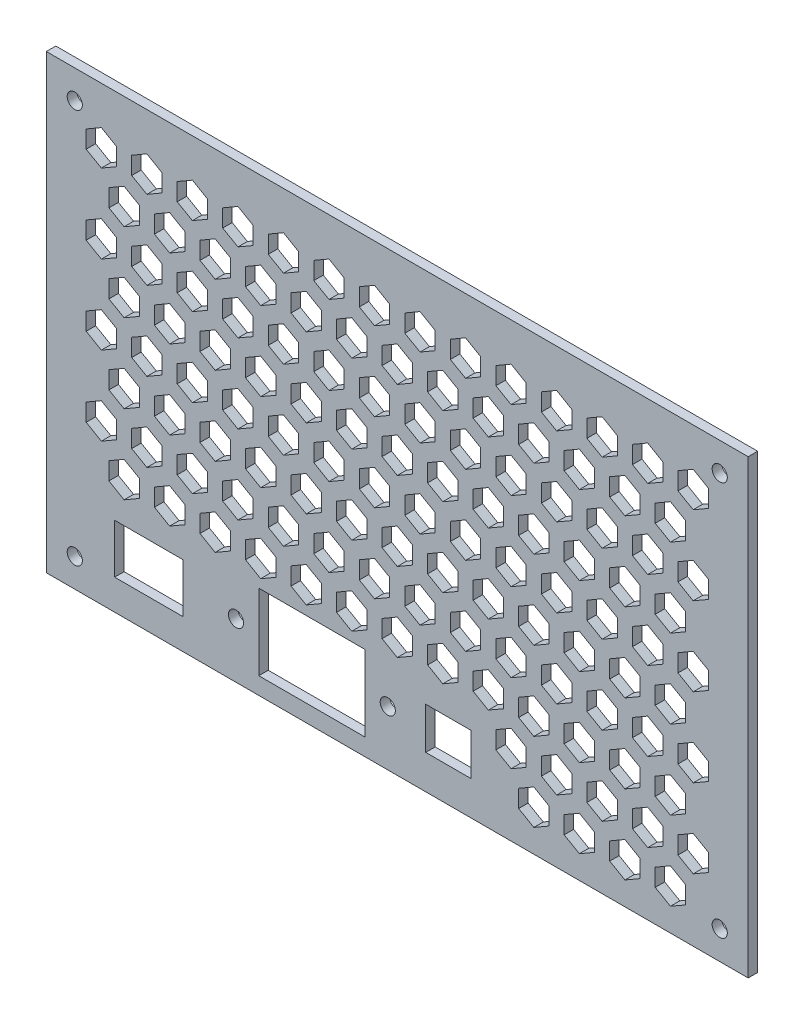
SolidWorks part; units mm, degrees
ref_plane "Front Plane" through (0, 0, 0) normal (0, 0, 1) x (1, 0, 0)
ref_plane "Top Plane" through (0, 0, 0) normal (0, 1, 0) x (1, 0, 0)
ref_plane "Right Plane" through (0, 0, 0) normal (1, 0, 0) x (0, 0, -1)
sketch "Sketch1" plane through (0, 0, 0) normal (0, 0, 1) x (1, 0, 0)
  line L1 (-92.5, -57.5) -> (92.5, -57.5)
  line L2 (-92.5, -57.5) -> (-92.5, 57.5)
  line L3 (-92.5, 57.5) -> (92.5, 57.5)
  line L4 (92.5, -57.5) -> (92.5, 57.5)
  line L5 (-92.5, -57.5) -> (92.5, 57.5) construction
  line L6 (-92.5, 57.5) -> (92.5, -57.5) construction
  point P0 (0, 0)
  dimension "D1" = 185
  dimension "D2" = 115
extrude "Boss-Extrude1" add sketch "Sketch1" along normal blind 2.5
sketch "Sketch2" plane through (0, 0, 0) normal (0, 0, -1) x (-1, 0, 0)
  line L0 (92.5, 57.5) -> (92.5, -57.5) construction
  line L1 (74.5, -36.5) -> (56.5, -36.5)
  line L2 (74.5, -36.5) -> (74.5, -49.5)
  line L3 (74.5, -49.5) -> (56.5, -49.5)
  line L4 (56.5, -36.5) -> (56.5, -49.5)
  line L5 (74.5, -36.5) -> (56.5, -49.5) construction
  line L6 (74.5, -49.5) -> (56.5, -36.5) construction
  line L8 (92.5, -57.5) -> (-92.5, -57.5) construction
  line L9 (36.5, -33) -> (8.5, -33)
  line L10 (36.5, -33) -> (36.5, -53)
  line L11 (36.5, -53) -> (8.5, -53)
  line L12 (8.5, -33) -> (8.5, -53)
  line L13 (36.5, -33) -> (8.5, -53) construction
  line L14 (36.5, -53) -> (8.5, -33) construction
  circle A0 centre (42.5, -43) radius 2
  circle A1 centre (2.5, -43) radius 2
  point P0 (65.5, -43)
  point P9 (22.5, -43)
  dimension "D7" = 4
  dimension "D8" = 4
  dimension "D9" = 20
  dimension "D10" = 20
  dimension "D1" = 18
  dimension "D2" = 13
  dimension "D3" = 18
  dimension "D4" = 8
  dimension "D5" = 28
  dimension "D6" = 20
  dimension "D11" = 70
extrude "Cut-Extrude1" cut sketch "Sketch2" against normal blind 10
sketch "Sketch4" plane through (0, 0, 0) normal (0, 0, -1) x (-1, 0, 0)
  text T0 "BACK" font "Century Gothic" height in points 72
extrude "Cut-Extrude2" [suppressed] cut sketch "Sketch4" against normal blind 1
sketch "Sketch5" plane through (0, 0, 0) normal (0, 0, -1) x (-1, 0, 0)
  line L24 (-72, 40.9827) -> (-76, 38.6733)
  line L25 (-78, 51.375) -> (-82, 49.0656)
  line L26 (-82, 49.0656) -> (-82, 44.4468)
  line L27 (-82, 44.4468) -> (-78, 42.1374)
  line L28 (-78, 42.1374) -> (-74, 44.4468)
  line L29 (-74, 44.4468) -> (-74, 49.0656)
  line L30 (-74, 49.0656) -> (-78, 51.375)
  line L31 (-76, 38.6733) -> (-76, 34.0545)
  line L32 (-76, 34.0545) -> (-72, 31.7451)
  line L33 (-72, 31.7451) -> (-68, 34.0545)
  line L34 (-68, 34.0545) -> (-68, 38.6733)
  line L35 (-68, 38.6733) -> (-72, 40.9827)
  line L36 (-60, 40.9827) -> (-64, 38.6733)
  line L37 (-66, 51.375) -> (-70, 49.0656)
  line L38 (-70, 49.0656) -> (-70, 44.4468)
  line L39 (-70, 44.4468) -> (-66, 42.1374)
  line L40 (-66, 42.1374) -> (-62, 44.4468)
  line L41 (-62, 44.4468) -> (-62, 49.0656)
  line L42 (-62, 49.0656) -> (-66, 51.375)
  line L43 (-64, 38.6733) -> (-64, 34.0545)
  line L44 (-64, 34.0545) -> (-60, 31.7451)
  line L45 (-60, 31.7451) -> (-56, 34.0545)
  line L46 (-56, 34.0545) -> (-56, 38.6733)
  line L47 (-56, 38.6733) -> (-60, 40.9827)
  line L48 (-48, 40.9827) -> (-52, 38.6733)
  line L49 (-54, 51.375) -> (-58, 49.0656)
  line L50 (-58, 49.0656) -> (-58, 44.4468)
  line L51 (-58, 44.4468) -> (-54, 42.1374)
  line L52 (-54, 42.1374) -> (-50, 44.4468)
  line L53 (-50, 44.4468) -> (-50, 49.0656)
  line L54 (-50, 49.0656) -> (-54, 51.375)
  line L55 (-52, 38.6733) -> (-52, 34.0545)
  line L56 (-52, 34.0545) -> (-48, 31.7451)
  line L57 (-48, 31.7451) -> (-44, 34.0545)
  line L58 (-44, 34.0545) -> (-44, 38.6733)
  line L59 (-44, 38.6733) -> (-48, 40.9827)
  line L60 (-36, 40.9827) -> (-40, 38.6733)
  line L61 (-42, 51.375) -> (-46, 49.0656)
  line L62 (-46, 49.0656) -> (-46, 44.4468)
  line L63 (-46, 44.4468) -> (-42, 42.1374)
  line L64 (-42, 42.1374) -> (-38, 44.4468)
  line L65 (-38, 44.4468) -> (-38, 49.0656)
  line L66 (-38, 49.0656) -> (-42, 51.375)
  line L67 (-40, 38.6733) -> (-40, 34.0545)
  line L68 (-40, 34.0545) -> (-36, 31.7451)
  line L69 (-36, 31.7451) -> (-32, 34.0545)
  line L70 (-32, 34.0545) -> (-32, 38.6733)
  line L71 (-32, 38.6733) -> (-36, 40.9827)
  line L72 (-24, 40.9827) -> (-28, 38.6733)
  line L73 (-30, 51.375) -> (-34, 49.0656)
  line L74 (-34, 49.0656) -> (-34, 44.4468)
  line L75 (-34, 44.4468) -> (-30, 42.1374)
  line L76 (-30, 42.1374) -> (-26, 44.4468)
  line L77 (-26, 44.4468) -> (-26, 49.0656)
  line L78 (-26, 49.0656) -> (-30, 51.375)
  line L79 (-28, 38.6733) -> (-28, 34.0545)
  line L80 (-28, 34.0545) -> (-24, 31.7451)
  line L81 (-24, 31.7451) -> (-20, 34.0545)
  line L82 (-20, 34.0545) -> (-20, 38.6733)
  line L83 (-20, 38.6733) -> (-24, 40.9827)
  line L84 (-12, 40.9827) -> (-16, 38.6733)
  line L85 (-18, 51.375) -> (-22, 49.0656)
  line L86 (-22, 49.0656) -> (-22, 44.4468)
  line L87 (-22, 44.4468) -> (-18, 42.1374)
  line L88 (-18, 42.1374) -> (-14, 44.4468)
  line L89 (-14, 44.4468) -> (-14, 49.0656)
  line L90 (-14, 49.0656) -> (-18, 51.375)
  line L91 (-16, 38.6733) -> (-16, 34.0545)
  line L92 (-16, 34.0545) -> (-12, 31.7451)
  line L93 (-12, 31.7451) -> (-8, 34.0545)
  line L94 (-8, 34.0545) -> (-8, 38.6733)
  line L95 (-8, 38.6733) -> (-12, 40.9827)
  line L96 (0, 40.9827) -> (-4, 38.6733)
  line L97 (-6, 51.375) -> (-10, 49.0656)
  line L98 (-10, 49.0656) -> (-10, 44.4468)
  line L99 (-10, 44.4468) -> (-6, 42.1374)
  line L100 (-6, 42.1374) -> (-2, 44.4468)
  line L101 (-2, 44.4468) -> (-2, 49.0656)
  line L102 (-2, 49.0656) -> (-6, 51.375)
  line L103 (-4, 38.6733) -> (-4, 34.0545)
  line L104 (-4, 34.0545) -> (0, 31.7451)
  line L105 (0, 31.7451) -> (4, 34.0545)
  line L106 (4, 34.0545) -> (4, 38.6733)
  line L107 (4, 38.6733) -> (0, 40.9827)
  line L108 (12, 40.9827) -> (8, 38.6733)
  line L109 (6, 51.375) -> (2, 49.0656)
  line L110 (2, 49.0656) -> (2, 44.4468)
  line L111 (2, 44.4468) -> (6, 42.1374)
  line L112 (6, 42.1374) -> (10, 44.4468)
  line L113 (10, 44.4468) -> (10, 49.0656)
  line L114 (10, 49.0656) -> (6, 51.375)
  line L115 (8, 38.6733) -> (8, 34.0545)
  line L116 (8, 34.0545) -> (12, 31.7451)
  line L117 (12, 31.7451) -> (16, 34.0545)
  line L118 (16, 34.0545) -> (16, 38.6733)
  line L119 (16, 38.6733) -> (12, 40.9827)
  line L120 (24, 40.9827) -> (20, 38.6733)
  line L121 (18, 51.375) -> (14, 49.0656)
  line L122 (14, 49.0656) -> (14, 44.4468)
  line L123 (14, 44.4468) -> (18, 42.1374)
  line L124 (18, 42.1374) -> (22, 44.4468)
  line L125 (22, 44.4468) -> (22, 49.0656)
  line L126 (22, 49.0656) -> (18, 51.375)
  line L127 (20, 38.6733) -> (20, 34.0545)
  line L128 (20, 34.0545) -> (24, 31.7451)
  line L129 (24, 31.7451) -> (28, 34.0545)
  line L130 (28, 34.0545) -> (28, 38.6733)
  line L131 (28, 38.6733) -> (24, 40.9827)
  line L132 (36, 40.9827) -> (32, 38.6733)
  line L133 (30, 51.375) -> (26, 49.0656)
  line L134 (26, 49.0656) -> (26, 44.4468)
  line L135 (26, 44.4468) -> (30, 42.1374)
  line L136 (30, 42.1374) -> (34, 44.4468)
  line L137 (34, 44.4468) -> (34, 49.0656)
  line L138 (34, 49.0656) -> (30, 51.375)
  line L139 (32, 38.6733) -> (32, 34.0545)
  line L140 (32, 34.0545) -> (36, 31.7451)
  line L141 (36, 31.7451) -> (40, 34.0545)
  line L142 (40, 34.0545) -> (40, 38.6733)
  line L143 (40, 38.6733) -> (36, 40.9827)
  line L144 (48, 40.9827) -> (44, 38.6733)
  line L145 (42, 51.375) -> (38, 49.0656)
  line L146 (38, 49.0656) -> (38, 44.4468)
  line L147 (38, 44.4468) -> (42, 42.1374)
  line L148 (42, 42.1374) -> (46, 44.4468)
  line L149 (46, 44.4468) -> (46, 49.0656)
  line L150 (46, 49.0656) -> (42, 51.375)
  line L151 (44, 38.6733) -> (44, 34.0545)
  line L152 (44, 34.0545) -> (48, 31.7451)
  line L153 (48, 31.7451) -> (52, 34.0545)
  line L154 (52, 34.0545) -> (52, 38.6733)
  line L155 (52, 38.6733) -> (48, 40.9827)
  line L156 (60, 40.9827) -> (56, 38.6733)
  line L157 (54, 51.375) -> (50, 49.0656)
  line L158 (50, 49.0656) -> (50, 44.4468)
  line L159 (50, 44.4468) -> (54, 42.1374)
  line L160 (54, 42.1374) -> (58, 44.4468)
  line L161 (58, 44.4468) -> (58, 49.0656)
  line L162 (58, 49.0656) -> (54, 51.375)
  line L163 (56, 38.6733) -> (56, 34.0545)
  line L164 (56, 34.0545) -> (60, 31.7451)
  line L165 (60, 31.7451) -> (64, 34.0545)
  line L166 (64, 34.0545) -> (64, 38.6733)
  line L167 (64, 38.6733) -> (60, 40.9827)
  line L168 (72, 40.9827) -> (68, 38.6733)
  line L169 (66, 51.375) -> (62, 49.0656)
  line L170 (62, 49.0656) -> (62, 44.4468)
  line L171 (62, 44.4468) -> (66, 42.1374)
  line L172 (66, 42.1374) -> (70, 44.4468)
  line L173 (70, 44.4468) -> (70, 49.0656)
  line L174 (70, 49.0656) -> (66, 51.375)
  line L175 (68, 38.6733) -> (68, 34.0545)
  line L176 (68, 34.0545) -> (72, 31.7451)
  line L177 (72, 31.7451) -> (76, 34.0545)
  line L178 (76, 34.0545) -> (76, 38.6733)
  line L179 (76, 38.6733) -> (72, 40.9827)
  line L180 (-60, 20.2027) -> (-64, 17.8933)
  line L181 (-66, 30.595) -> (-70, 28.2856)
  line L182 (-70, 28.2856) -> (-70, 23.6668)
  line L183 (-70, 23.6668) -> (-66, 21.3574)
  line L184 (-66, 21.3574) -> (-62, 23.6668)
  line L185 (-62, 23.6668) -> (-62, 28.2856)
  line L186 (-62, 28.2856) -> (-66, 30.595)
  line L187 (-64, 17.8933) -> (-64, 13.2745)
  line L188 (-64, 13.2745) -> (-60, 10.9651)
  line L189 (-60, 10.9651) -> (-56, 13.2745)
  line L190 (-56, 13.2745) -> (-56, 17.8933)
  line L191 (-56, 17.8933) -> (-60, 20.2027)
  line L192 (-48, 20.2027) -> (-52, 17.8933)
  line L193 (-54, 30.595) -> (-58, 28.2856)
  line L194 (-58, 28.2856) -> (-58, 23.6668)
  line L195 (-58, 23.6668) -> (-54, 21.3574)
  line L196 (-54, 21.3574) -> (-50, 23.6668)
  line L197 (-50, 23.6668) -> (-50, 28.2856)
  line L198 (-50, 28.2856) -> (-54, 30.595)
  line L199 (-52, 17.8933) -> (-52, 13.2745)
  line L200 (-52, 13.2745) -> (-48, 10.9651)
  line L201 (-48, 10.9651) -> (-44, 13.2745)
  line L202 (-44, 13.2745) -> (-44, 17.8933)
  line L203 (-44, 17.8933) -> (-48, 20.2027)
  line L204 (-36, 20.2027) -> (-40, 17.8933)
  line L205 (-42, 30.595) -> (-46, 28.2856)
  line L206 (-46, 28.2856) -> (-46, 23.6668)
  line L207 (-46, 23.6668) -> (-42, 21.3574)
  line L208 (-42, 21.3574) -> (-38, 23.6668)
  line L209 (-38, 23.6668) -> (-38, 28.2856)
  line L210 (-38, 28.2856) -> (-42, 30.595)
  line L211 (-40, 17.8933) -> (-40, 13.2745)
  line L212 (-40, 13.2745) -> (-36, 10.9651)
  line L213 (-36, 10.9651) -> (-32, 13.2745)
  line L214 (-32, 13.2745) -> (-32, 17.8933)
  line L215 (-32, 17.8933) -> (-36, 20.2027)
  line L216 (-24, 20.2027) -> (-28, 17.8933)
  line L217 (-30, 30.595) -> (-34, 28.2856)
  line L218 (-34, 28.2856) -> (-34, 23.6668)
  line L219 (-34, 23.6668) -> (-30, 21.3574)
  line L220 (-30, 21.3574) -> (-26, 23.6668)
  line L221 (-26, 23.6668) -> (-26, 28.2856)
  line L222 (-26, 28.2856) -> (-30, 30.595)
  line L223 (-28, 17.8933) -> (-28, 13.2745)
  line L224 (-28, 13.2745) -> (-24, 10.9651)
  line L225 (-24, 10.9651) -> (-20, 13.2745)
  line L226 (-20, 13.2745) -> (-20, 17.8933)
  line L227 (-20, 17.8933) -> (-24, 20.2027)
  line L228 (-12, 20.2027) -> (-16, 17.8933)
  line L229 (-18, 30.595) -> (-22, 28.2856)
  line L230 (-22, 28.2856) -> (-22, 23.6668)
  line L231 (-22, 23.6668) -> (-18, 21.3574)
  line L232 (-18, 21.3574) -> (-14, 23.6668)
  line L233 (-14, 23.6668) -> (-14, 28.2856)
  line L234 (-14, 28.2856) -> (-18, 30.595)
  line L235 (-16, 17.8933) -> (-16, 13.2745)
  line L236 (-16, 13.2745) -> (-12, 10.9651)
  line L237 (-12, 10.9651) -> (-8, 13.2745)
  line L238 (-8, 13.2745) -> (-8, 17.8933)
  line L239 (-8, 17.8933) -> (-12, 20.2027)
  line L240 (0, 20.2027) -> (-4, 17.8933)
  line L241 (-6, 30.595) -> (-10, 28.2856)
  line L242 (-10, 28.2856) -> (-10, 23.6668)
  line L243 (-10, 23.6668) -> (-6, 21.3574)
  line L244 (-6, 21.3574) -> (-2, 23.6668)
  line L245 (-2, 23.6668) -> (-2, 28.2856)
  line L246 (-2, 28.2856) -> (-6, 30.595)
  line L247 (-4, 17.8933) -> (-4, 13.2745)
  line L248 (-4, 13.2745) -> (0, 10.9651)
  line L249 (0, 10.9651) -> (4, 13.2745)
  line L250 (4, 13.2745) -> (4, 17.8933)
  line L251 (4, 17.8933) -> (0, 20.2027)
  line L252 (12, 20.2027) -> (8, 17.8933)
  line L253 (6, 30.595) -> (2, 28.2856)
  line L254 (2, 28.2856) -> (2, 23.6668)
  line L255 (2, 23.6668) -> (6, 21.3574)
  line L256 (6, 21.3574) -> (10, 23.6668)
  line L257 (10, 23.6668) -> (10, 28.2856)
  line L258 (10, 28.2856) -> (6, 30.595)
  line L259 (8, 17.8933) -> (8, 13.2745)
  line L260 (8, 13.2745) -> (12, 10.9651)
  line L261 (12, 10.9651) -> (16, 13.2745)
  line L262 (16, 13.2745) -> (16, 17.8933)
  line L263 (16, 17.8933) -> (12, 20.2027)
  line L264 (24, 20.2027) -> (20, 17.8933)
  line L265 (18, 30.595) -> (14, 28.2856)
  line L266 (14, 28.2856) -> (14, 23.6668)
  line L267 (14, 23.6668) -> (18, 21.3574)
  line L268 (18, 21.3574) -> (22, 23.6668)
  line L269 (22, 23.6668) -> (22, 28.2856)
  line L270 (22, 28.2856) -> (18, 30.595)
  line L271 (20, 17.8933) -> (20, 13.2745)
  line L272 (20, 13.2745) -> (24, 10.9651)
  line L273 (24, 10.9651) -> (28, 13.2745)
  line L274 (28, 13.2745) -> (28, 17.8933)
  line L275 (28, 17.8933) -> (24, 20.2027)
  line L276 (36, 20.2027) -> (32, 17.8933)
  line L277 (30, 30.595) -> (26, 28.2856)
  line L278 (26, 28.2856) -> (26, 23.6668)
  line L279 (26, 23.6668) -> (30, 21.3574)
  line L280 (30, 21.3574) -> (34, 23.6668)
  line L281 (34, 23.6668) -> (34, 28.2856)
  line L282 (34, 28.2856) -> (30, 30.595)
  line L283 (32, 17.8933) -> (32, 13.2745)
  line L284 (32, 13.2745) -> (36, 10.9651)
  line L285 (36, 10.9651) -> (40, 13.2745)
  line L286 (40, 13.2745) -> (40, 17.8933)
  line L287 (40, 17.8933) -> (36, 20.2027)
  line L288 (48, 20.2027) -> (44, 17.8933)
  line L289 (42, 30.595) -> (38, 28.2856)
  line L290 (38, 28.2856) -> (38, 23.6668)
  line L291 (38, 23.6668) -> (42, 21.3574)
  line L292 (42, 21.3574) -> (46, 23.6668)
  line L293 (46, 23.6668) -> (46, 28.2856)
  line L294 (46, 28.2856) -> (42, 30.595)
  line L295 (44, 17.8933) -> (44, 13.2745)
  line L296 (44, 13.2745) -> (48, 10.9651)
  line L297 (48, 10.9651) -> (52, 13.2745)
  line L298 (52, 13.2745) -> (52, 17.8933)
  line L299 (52, 17.8933) -> (48, 20.2027)
  line L300 (60, 20.2027) -> (56, 17.8933)
  line L301 (54, 30.595) -> (50, 28.2856)
  line L302 (50, 28.2856) -> (50, 23.6668)
  line L303 (50, 23.6668) -> (54, 21.3574)
  line L304 (54, 21.3574) -> (58, 23.6668)
  line L305 (58, 23.6668) -> (58, 28.2856)
  line L306 (58, 28.2856) -> (54, 30.595)
  line L307 (56, 17.8933) -> (56, 13.2745)
  line L308 (56, 13.2745) -> (60, 10.9651)
  line L309 (60, 10.9651) -> (64, 13.2745)
  line L310 (64, 13.2745) -> (64, 17.8933)
  line L311 (64, 17.8933) -> (60, 20.2027)
  line L312 (72, 20.2027) -> (68, 17.8933)
  line L313 (66, 30.595) -> (62, 28.2856)
  line L314 (62, 28.2856) -> (62, 23.6668)
  line L315 (62, 23.6668) -> (66, 21.3574)
  line L316 (66, 21.3574) -> (70, 23.6668)
  line L317 (70, 23.6668) -> (70, 28.2856)
  line L318 (70, 28.2856) -> (66, 30.595)
  line L319 (68, 17.8933) -> (68, 13.2745)
  line L320 (68, 13.2745) -> (72, 10.9651)
  line L321 (72, 10.9651) -> (76, 13.2745)
  line L322 (76, 13.2745) -> (76, 17.8933)
  line L323 (76, 17.8933) -> (72, 20.2027)
  line L324 (-60, -0.5773) -> (-64, -2.8867)
  line L325 (-66, 9.815) -> (-70, 7.5056)
  line L326 (-70, 7.5056) -> (-70, 2.8868)
  line L327 (-70, 2.8868) -> (-66, 0.5774)
  line L328 (-66, 0.5774) -> (-62, 2.8868)
  line L329 (-62, 2.8868) -> (-62, 7.5056)
  line L330 (-62, 7.5056) -> (-66, 9.815)
  line L331 (-64, -2.8867) -> (-64, -7.5055)
  line L332 (-64, -7.5055) -> (-60, -9.8149)
  line L333 (-60, -9.8149) -> (-56, -7.5055)
  line L334 (-56, -7.5055) -> (-56, -2.8867)
  line L335 (-56, -2.8867) -> (-60, -0.5773)
  line L336 (-48, -0.5773) -> (-52, -2.8867)
  line L337 (-54, 9.815) -> (-58, 7.5056)
  line L338 (-58, 7.5056) -> (-58, 2.8868)
  line L339 (-58, 2.8868) -> (-54, 0.5774)
  line L340 (-54, 0.5774) -> (-50, 2.8868)
  line L341 (-50, 2.8868) -> (-50, 7.5056)
  line L342 (-50, 7.5056) -> (-54, 9.815)
  line L343 (-52, -2.8867) -> (-52, -7.5055)
  line L344 (-52, -7.5055) -> (-48, -9.8149)
  line L345 (-48, -9.8149) -> (-44, -7.5055)
  line L346 (-44, -7.5055) -> (-44, -2.8867)
  line L347 (-44, -2.8867) -> (-48, -0.5773)
  line L348 (-36, -0.5773) -> (-40, -2.8867)
  line L349 (-42, 9.815) -> (-46, 7.5056)
  line L350 (-46, 7.5056) -> (-46, 2.8868)
  line L351 (-46, 2.8868) -> (-42, 0.5774)
  line L352 (-42, 0.5774) -> (-38, 2.8868)
  line L353 (-38, 2.8868) -> (-38, 7.5056)
  line L354 (-38, 7.5056) -> (-42, 9.815)
  line L355 (-40, -2.8867) -> (-40, -7.5055)
  line L356 (-40, -7.5055) -> (-36, -9.8149)
  line L357 (-36, -9.8149) -> (-32, -7.5055)
  line L358 (-32, -7.5055) -> (-32, -2.8867)
  line L359 (-32, -2.8867) -> (-36, -0.5773)
  line L360 (-24, -0.5773) -> (-28, -2.8867)
  line L361 (-30, 9.815) -> (-34, 7.5056)
  line L362 (-34, 7.5056) -> (-34, 2.8868)
  line L363 (-34, 2.8868) -> (-30, 0.5774)
  line L364 (-30, 0.5774) -> (-26, 2.8868)
  line L365 (-26, 2.8868) -> (-26, 7.5056)
  line L366 (-26, 7.5056) -> (-30, 9.815)
  line L367 (-28, -2.8867) -> (-28, -7.5055)
  line L368 (-28, -7.5055) -> (-24, -9.8149)
  line L369 (-24, -9.8149) -> (-20, -7.5055)
  line L370 (-20, -7.5055) -> (-20, -2.8867)
  line L371 (-20, -2.8867) -> (-24, -0.5773)
  line L372 (-12, -0.5773) -> (-16, -2.8867)
  line L373 (-18, 9.815) -> (-22, 7.5056)
  line L374 (-22, 7.5056) -> (-22, 2.8868)
  line L375 (-22, 2.8868) -> (-18, 0.5774)
  line L376 (-18, 0.5774) -> (-14, 2.8868)
  line L377 (-14, 2.8868) -> (-14, 7.5056)
  line L378 (-14, 7.5056) -> (-18, 9.815)
  line L379 (-16, -2.8867) -> (-16, -7.5055)
  line L380 (-16, -7.5055) -> (-12, -9.8149)
  line L381 (-12, -9.8149) -> (-8, -7.5055)
  line L382 (-8, -7.5055) -> (-8, -2.8867)
  line L383 (-8, -2.8867) -> (-12, -0.5773)
  line L384 (0, -0.5773) -> (-4, -2.8867)
  line L385 (-6, 9.815) -> (-10, 7.5056)
  line L386 (-10, 7.5056) -> (-10, 2.8868)
  line L387 (-10, 2.8868) -> (-6, 0.5774)
  line L388 (-6, 0.5774) -> (-2, 2.8868)
  line L389 (-2, 2.8868) -> (-2, 7.5056)
  line L390 (-2, 7.5056) -> (-6, 9.815)
  line L391 (-4, -2.8867) -> (-4, -7.5055)
  line L392 (-4, -7.5055) -> (0, -9.8149)
  line L393 (0, -9.8149) -> (4, -7.5055)
  line L394 (4, -7.5055) -> (4, -2.8867)
  line L395 (4, -2.8867) -> (0, -0.5773)
  line L396 (12, -0.5773) -> (8, -2.8867)
  line L397 (6, 9.815) -> (2, 7.5056)
  line L398 (2, 7.5056) -> (2, 2.8868)
  line L399 (2, 2.8868) -> (6, 0.5774)
  line L400 (6, 0.5774) -> (10, 2.8868)
  line L401 (10, 2.8868) -> (10, 7.5056)
  line L402 (10, 7.5056) -> (6, 9.815)
  line L403 (8, -2.8867) -> (8, -7.5055)
  line L404 (8, -7.5055) -> (12, -9.8149)
  line L405 (12, -9.8149) -> (16, -7.5055)
  line L406 (16, -7.5055) -> (16, -2.8867)
  line L407 (16, -2.8867) -> (12, -0.5773)
  line L408 (24, -0.5773) -> (20, -2.8867)
  line L409 (18, 9.815) -> (14, 7.5056)
  line L410 (14, 7.5056) -> (14, 2.8868)
  line L411 (14, 2.8868) -> (18, 0.5774)
  line L412 (18, 0.5774) -> (22, 2.8868)
  line L413 (22, 2.8868) -> (22, 7.5056)
  line L414 (22, 7.5056) -> (18, 9.815)
  line L415 (20, -2.8867) -> (20, -7.5055)
  line L416 (20, -7.5055) -> (24, -9.8149)
  line L417 (24, -9.8149) -> (28, -7.5055)
  line L418 (28, -7.5055) -> (28, -2.8867)
  line L419 (28, -2.8867) -> (24, -0.5773)
  line L420 (36, -0.5773) -> (32, -2.8867)
  line L421 (30, 9.815) -> (26, 7.5056)
  line L422 (26, 7.5056) -> (26, 2.8868)
  line L423 (26, 2.8868) -> (30, 0.5774)
  line L424 (30, 0.5774) -> (34, 2.8868)
  line L425 (34, 2.8868) -> (34, 7.5056)
  line L426 (34, 7.5056) -> (30, 9.815)
  line L427 (32, -2.8867) -> (32, -7.5055)
  line L428 (32, -7.5055) -> (36, -9.8149)
  line L429 (36, -9.8149) -> (40, -7.5055)
  line L430 (40, -7.5055) -> (40, -2.8867)
  line L431 (40, -2.8867) -> (36, -0.5773)
  line L432 (48, -0.5773) -> (44, -2.8867)
  line L433 (42, 9.815) -> (38, 7.5056)
  line L434 (38, 7.5056) -> (38, 2.8868)
  line L435 (38, 2.8868) -> (42, 0.5774)
  line L436 (42, 0.5774) -> (46, 2.8868)
  line L437 (46, 2.8868) -> (46, 7.5056)
  line L438 (46, 7.5056) -> (42, 9.815)
  line L439 (44, -2.8867) -> (44, -7.5055)
  line L440 (44, -7.5055) -> (48, -9.8149)
  line L441 (48, -9.8149) -> (52, -7.5055)
  line L442 (52, -7.5055) -> (52, -2.8867)
  line L443 (52, -2.8867) -> (48, -0.5773)
  line L444 (60, -0.5773) -> (56, -2.8867)
  line L445 (54, 9.815) -> (50, 7.5056)
  line L446 (50, 7.5056) -> (50, 2.8868)
  line L447 (50, 2.8868) -> (54, 0.5774)
  line L448 (54, 0.5774) -> (58, 2.8868)
  line L449 (58, 2.8868) -> (58, 7.5056)
  line L450 (58, 7.5056) -> (54, 9.815)
  line L451 (56, -2.8867) -> (56, -7.5055)
  line L452 (56, -7.5055) -> (60, -9.8149)
  line L453 (60, -9.8149) -> (64, -7.5055)
  line L454 (64, -7.5055) -> (64, -2.8867)
  line L455 (64, -2.8867) -> (60, -0.5773)
  line L456 (72, -0.5773) -> (68, -2.8867)
  line L457 (66, 9.815) -> (62, 7.5056)
  line L458 (62, 7.5056) -> (62, 2.8868)
  line L459 (62, 2.8868) -> (66, 0.5774)
  line L460 (66, 0.5774) -> (70, 2.8868)
  line L461 (70, 2.8868) -> (70, 7.5056)
  line L462 (70, 7.5056) -> (66, 9.815)
  line L463 (68, -2.8867) -> (68, -7.5055)
  line L464 (68, -7.5055) -> (72, -9.8149)
  line L465 (72, -9.8149) -> (76, -7.5055)
  line L466 (76, -7.5055) -> (76, -2.8867)
  line L467 (76, -2.8867) -> (72, -0.5773)
  line L468 (-72, 20.2027) -> (-76, 17.8933)
  line L469 (-78, 30.595) -> (-82, 28.2856)
  line L470 (-82, 28.2856) -> (-82, 23.6668)
  line L471 (-82, 23.6668) -> (-78, 21.3574)
  line L472 (-78, 21.3574) -> (-74, 23.6668)
  line L473 (-74, 23.6668) -> (-74, 28.2856)
  line L474 (-74, 28.2856) -> (-78, 30.595)
  line L475 (-76, 17.8933) -> (-76, 13.2745)
  line L476 (-76, 13.2745) -> (-72, 10.9651)
  line L477 (-72, 10.9651) -> (-68, 13.2745)
  line L478 (-68, 13.2745) -> (-68, 17.8933)
  line L479 (-68, 17.8933) -> (-72, 20.2027)
  line L480 (-72, -0.5773) -> (-76, -2.8867)
  line L481 (-78, 9.815) -> (-82, 7.5056)
  line L482 (-82, 7.5056) -> (-82, 2.8868)
  line L483 (-82, 2.8868) -> (-78, 0.5774)
  line L484 (-78, 0.5774) -> (-74, 2.8868)
  line L485 (-74, 2.8868) -> (-74, 7.5056)
  line L486 (-74, 7.5056) -> (-78, 9.815)
  line L487 (-76, -2.8867) -> (-76, -7.5055)
  line L488 (-76, -7.5055) -> (-72, -9.8149)
  line L489 (-72, -9.8149) -> (-68, -7.5055)
  line L490 (-68, -7.5055) -> (-68, -2.8867)
  line L491 (-68, -2.8867) -> (-72, -0.5773)
  line L492 (-92.5, -57.5) -> (-92.5, 57.5) construction
  line L565 (-72, -21.3573) -> (-76, -23.6667)
  line L566 (78, 51.375) -> (74, 49.0656)
  line L567 (74, 49.0656) -> (74, 44.4468)
  line L568 (74, 44.4468) -> (78, 42.1374)
  line L569 (78, 42.1374) -> (82, 44.4468)
  line L570 (82, 44.4468) -> (82, 49.0656)
  line L571 (82, 49.0656) -> (78, 51.375)
  line L572 (-78, -10.965) -> (-82, -13.2744)
  line L573 (-92.5, 57.5) -> (92.5, 57.5) construction
  line L574 (-82, -13.2744) -> (-82, -17.8932)
  line L575 (-82, -17.8932) -> (-78, -20.2026)
  line L576 (-78, -20.2026) -> (-74, -17.8932)
  line L577 (-74, -17.8932) -> (-74, -13.2744)
  line L578 (-74, -13.2744) -> (-78, -10.965)
  line L579 (-76, -23.6667) -> (-76, -28.2855)
  line L580 (-76, -28.2855) -> (-72, -30.5949)
  line L581 (-72, -30.5949) -> (-68, -28.2855)
  line L582 (-68, -28.2855) -> (-68, -23.6667)
  line L583 (-68, -23.6667) -> (-72, -21.3573)
  line L584 (-60, -21.3573) -> (-64, -23.6667)
  line L585 (-66, -10.965) -> (-70, -13.2744)
  line L586 (-70, -13.2744) -> (-70, -17.8932)
  line L587 (-70, -17.8932) -> (-66, -20.2026)
  line L588 (-66, -20.2026) -> (-62, -17.8932)
  line L589 (-62, -17.8932) -> (-62, -13.2744)
  line L590 (-62, -13.2744) -> (-66, -10.965)
  line L591 (-64, -23.6667) -> (-64, -28.2855)
  line L592 (-64, -28.2855) -> (-60, -30.5949)
  line L593 (-60, -30.5949) -> (-56, -28.2855)
  line L594 (-56, -28.2855) -> (-56, -23.6667)
  line L595 (-56, -23.6667) -> (-60, -21.3573)
  line L596 (-48, -21.3573) -> (-52, -23.6667)
  line L597 (-54, -10.965) -> (-58, -13.2744)
  line L598 (-58, -13.2744) -> (-58, -17.8932)
  line L599 (-58, -17.8932) -> (-54, -20.2026)
  line L600 (-54, -20.2026) -> (-50, -17.8932)
  line L601 (-50, -17.8932) -> (-50, -13.2744)
  line L602 (-50, -13.2744) -> (-54, -10.965)
  line L603 (-52, -23.6667) -> (-52, -28.2855)
  line L604 (-52, -28.2855) -> (-48, -30.5949)
  line L605 (-48, -30.5949) -> (-44, -28.2855)
  line L606 (-44, -28.2855) -> (-44, -23.6667)
  line L607 (-44, -23.6667) -> (-48, -21.3573)
  line L608 (-36, -21.3573) -> (-40, -23.6667)
  line L609 (-42, -10.965) -> (-46, -13.2744)
  line L610 (-46, -13.2744) -> (-46, -17.8932)
  line L611 (-46, -17.8932) -> (-42, -20.2026)
  line L612 (-42, -20.2026) -> (-38, -17.8932)
  line L613 (-38, -17.8932) -> (-38, -13.2744)
  line L614 (-38, -13.2744) -> (-42, -10.965)
  line L615 (-40, -23.6667) -> (-40, -28.2855)
  line L616 (-40, -28.2855) -> (-36, -30.5949)
  line L617 (-36, -30.5949) -> (-32, -28.2855)
  line L618 (-32, -28.2855) -> (-32, -23.6667)
  line L619 (-32, -23.6667) -> (-36, -21.3573)
  line L620 (-24, -21.3573) -> (-28, -23.6667)
  line L621 (-30, -10.965) -> (-34, -13.2744)
  line L622 (-34, -13.2744) -> (-34, -17.8932)
  line L623 (-34, -17.8932) -> (-30, -20.2026)
  line L624 (-30, -20.2026) -> (-26, -17.8932)
  line L625 (-26, -17.8932) -> (-26, -13.2744)
  line L626 (-26, -13.2744) -> (-30, -10.965)
  line L627 (-28, -23.6667) -> (-28, -28.2855)
  line L628 (-28, -28.2855) -> (-24, -30.5949)
  line L629 (-24, -30.5949) -> (-20, -28.2855)
  line L630 (-20, -28.2855) -> (-20, -23.6667)
  line L631 (-20, -23.6667) -> (-24, -21.3573)
  line L632 (-12, -21.3573) -> (-16, -23.6667)
  line L633 (-18, -10.965) -> (-22, -13.2744)
  line L634 (-22, -13.2744) -> (-22, -17.8932)
  line L635 (-22, -17.8932) -> (-18, -20.2026)
  line L636 (-18, -20.2026) -> (-14, -17.8932)
  line L637 (-14, -17.8932) -> (-14, -13.2744)
  line L638 (-14, -13.2744) -> (-18, -10.965)
  line L639 (-16, -23.6667) -> (-16, -28.2855)
  line L640 (-16, -28.2855) -> (-12, -30.5949)
  line L641 (-12, -30.5949) -> (-8, -28.2855)
  line L642 (-8, -28.2855) -> (-8, -23.6667)
  line L643 (-8, -23.6667) -> (-12, -21.3573)
  line L644 (0, -21.3573) -> (-4, -23.6667)
  line L645 (-6, -10.965) -> (-10, -13.2744)
  line L646 (-10, -13.2744) -> (-10, -17.8932)
  line L647 (-10, -17.8932) -> (-6, -20.2026)
  line L648 (-6, -20.2026) -> (-2, -17.8932)
  line L649 (-2, -17.8932) -> (-2, -13.2744)
  line L650 (-2, -13.2744) -> (-6, -10.965)
  line L651 (-4, -23.6667) -> (-4, -28.2855)
  line L652 (-4, -28.2855) -> (0, -30.5949)
  line L653 (0, -30.5949) -> (4, -28.2855)
  line L654 (4, -28.2855) -> (4, -23.6667)
  line L655 (4, -23.6667) -> (0, -21.3573)
  line L656 (12, -21.3573) -> (8, -23.6667)
  line L657 (6, -10.965) -> (2, -13.2744)
  line L658 (2, -13.2744) -> (2, -17.8932)
  line L659 (2, -17.8932) -> (6, -20.2026)
  line L660 (6, -20.2026) -> (10, -17.8932)
  line L661 (10, -17.8932) -> (10, -13.2744)
  line L662 (10, -13.2744) -> (6, -10.965)
  line L663 (8, -23.6667) -> (8, -28.2855)
  line L664 (8, -28.2855) -> (12, -30.5949)
  line L665 (12, -30.5949) -> (16, -28.2855)
  line L666 (16, -28.2855) -> (16, -23.6667)
  line L667 (16, -23.6667) -> (12, -21.3573)
  line L668 (24, -21.3573) -> (20, -23.6667)
  line L669 (18, -10.965) -> (14, -13.2744)
  line L670 (14, -13.2744) -> (14, -17.8932)
  line L671 (14, -17.8932) -> (18, -20.2026)
  line L672 (18, -20.2026) -> (22, -17.8932)
  line L673 (22, -17.8932) -> (22, -13.2744)
  line L674 (22, -13.2744) -> (18, -10.965)
  line L675 (20, -23.6667) -> (20, -28.2855)
  line L676 (20, -28.2855) -> (24, -30.5949)
  line L677 (24, -30.5949) -> (28, -28.2855)
  line L678 (28, -28.2855) -> (28, -23.6667)
  line L679 (28, -23.6667) -> (24, -21.3573)
  line L680 (36, -21.3573) -> (32, -23.6667)
  line L681 (30, -10.965) -> (26, -13.2744)
  line L682 (26, -13.2744) -> (26, -17.8932)
  line L683 (26, -17.8932) -> (30, -20.2026)
  line L684 (30, -20.2026) -> (34, -17.8932)
  line L685 (34, -17.8932) -> (34, -13.2744)
  line L686 (34, -13.2744) -> (30, -10.965)
  line L687 (32, -23.6667) -> (32, -28.2855)
  line L688 (32, -28.2855) -> (36, -30.5949)
  line L689 (36, -30.5949) -> (40, -28.2855)
  line L690 (40, -28.2855) -> (40, -23.6667)
  line L691 (40, -23.6667) -> (36, -21.3573)
  line L692 (48, -21.3573) -> (44, -23.6667)
  line L693 (42, -10.965) -> (38, -13.2744)
  line L694 (38, -13.2744) -> (38, -17.8932)
  line L695 (38, -17.8932) -> (42, -20.2026)
  line L696 (42, -20.2026) -> (46, -17.8932)
  line L697 (46, -17.8932) -> (46, -13.2744)
  line L698 (46, -13.2744) -> (42, -10.965)
  line L699 (44, -23.6667) -> (44, -28.2855)
  line L700 (44, -28.2855) -> (48, -30.5949)
  line L701 (48, -30.5949) -> (52, -28.2855)
  line L702 (52, -28.2855) -> (52, -23.6667)
  line L703 (52, -23.6667) -> (48, -21.3573)
  line L704 (60, -21.3573) -> (56, -23.6667)
  line L705 (54, -10.965) -> (50, -13.2744)
  line L706 (50, -13.2744) -> (50, -17.8932)
  line L707 (50, -17.8932) -> (54, -20.2026)
  line L708 (54, -20.2026) -> (58, -17.8932)
  line L709 (58, -17.8932) -> (58, -13.2744)
  line L710 (58, -13.2744) -> (54, -10.965)
  line L711 (56, -23.6667) -> (56, -28.2855)
  line L712 (56, -28.2855) -> (60, -30.5949)
  line L713 (60, -30.5949) -> (64, -28.2855)
  line L714 (64, -28.2855) -> (64, -23.6667)
  line L715 (64, -23.6667) -> (60, -21.3573)
  line L716 (72, -21.3573) -> (68, -23.6667)
  line L717 (66, -10.965) -> (62, -13.2744)
  line L718 (62, -13.2744) -> (62, -17.8932)
  line L719 (62, -17.8932) -> (66, -20.2026)
  line L720 (66, -20.2026) -> (70, -17.8932)
  line L721 (70, -17.8932) -> (70, -13.2744)
  line L722 (70, -13.2744) -> (66, -10.965)
  line L723 (68, -23.6667) -> (68, -28.2855)
  line L724 (68, -28.2855) -> (72, -30.5949)
  line L725 (72, -30.5949) -> (76, -28.2855)
  line L726 (76, -28.2855) -> (76, -23.6667)
  line L727 (76, -23.6667) -> (72, -21.3573)
  line L740 (78, 30.595) -> (74, 28.2856)
  line L741 (74, 28.2856) -> (74, 23.6668)
  line L742 (74, 23.6668) -> (78, 21.3574)
  line L743 (78, 21.3574) -> (82, 23.6668)
  line L744 (82, 23.6668) -> (82, 28.2856)
  line L745 (82, 28.2856) -> (78, 30.595)
  line L746 (78, 9.815) -> (74, 7.5056)
  line L747 (74, 7.5056) -> (74, 2.8868)
  line L748 (74, 2.8868) -> (78, 0.5774)
  line L749 (78, 0.5774) -> (82, 2.8868)
  line L750 (82, 2.8868) -> (82, 7.5056)
  line L751 (82, 7.5056) -> (78, 9.815)
  line L752 (78, -10.965) -> (74, -13.2744)
  line L753 (74, -13.2744) -> (74, -17.8932)
  line L754 (74, -17.8932) -> (78, -20.2026)
  line L755 (78, -20.2026) -> (82, -17.8932)
  line L756 (82, -17.8932) -> (82, -13.2744)
  line L757 (82, -13.2744) -> (78, -10.965)
  line L758 (-72, -42.1373) -> (-76, -44.4467)
  line L759 (-78, -31.745) -> (-82, -34.0544)
  line L760 (-82, -34.0544) -> (-82, -38.6732)
  line L761 (-82, -38.6732) -> (-78, -40.9826)
  line L762 (-78, -40.9826) -> (-74, -38.6732)
  line L763 (-74, -38.6732) -> (-74, -34.0544)
  line L764 (-74, -34.0544) -> (-78, -31.745)
  line L765 (-76, -44.4467) -> (-76, -49.0655)
  line L766 (-76, -49.0655) -> (-72, -51.3749)
  line L767 (-72, -51.3749) -> (-68, -49.0655)
  line L768 (-68, -49.0655) -> (-68, -44.4467)
  line L769 (-68, -44.4467) -> (-72, -42.1373)
  line L770 (-60, -42.1373) -> (-64, -44.4467)
  line L771 (-66, -31.745) -> (-70, -34.0544)
  line L772 (-70, -34.0544) -> (-70, -38.6732)
  line L773 (-70, -38.6732) -> (-66, -40.9826)
  line L774 (-66, -40.9826) -> (-62, -38.6732)
  line L775 (-62, -38.6732) -> (-62, -34.0544)
  line L776 (-62, -34.0544) -> (-66, -31.745)
  line L777 (-64, -44.4467) -> (-64, -49.0655)
  line L778 (-64, -49.0655) -> (-60, -51.3749)
  line L779 (-60, -51.3749) -> (-56, -49.0655)
  line L780 (-56, -49.0655) -> (-56, -44.4467)
  line L781 (-56, -44.4467) -> (-60, -42.1373)
  line L782 (-48, -42.1373) -> (-52, -44.4467)
  line L783 (-54, -31.745) -> (-58, -34.0544)
  line L784 (-58, -34.0544) -> (-58, -38.6732)
  line L785 (-58, -38.6732) -> (-54, -40.9826)
  line L786 (-54, -40.9826) -> (-50, -38.6732)
  line L787 (-50, -38.6732) -> (-50, -34.0544)
  line L788 (-50, -34.0544) -> (-54, -31.745)
  line L789 (-52, -44.4467) -> (-52, -49.0655)
  line L790 (-52, -49.0655) -> (-48, -51.3749)
  line L791 (-48, -51.3749) -> (-44, -49.0655)
  line L792 (-44, -49.0655) -> (-44, -44.4467)
  line L793 (-44, -44.4467) -> (-48, -42.1373)
  line L794 (-36, -42.1373) -> (-40, -44.4467)
  line L795 (-42, -31.745) -> (-46, -34.0544)
  line L796 (-46, -34.0544) -> (-46, -38.6732)
  line L797 (-46, -38.6732) -> (-42, -40.9826)
  line L798 (-42, -40.9826) -> (-38, -38.6732)
  line L799 (-38, -38.6732) -> (-38, -34.0544)
  line L800 (-38, -34.0544) -> (-42, -31.745)
  line L801 (-40, -44.4467) -> (-40, -49.0655)
  line L802 (-40, -49.0655) -> (-36, -51.3749)
  line L803 (-36, -51.3749) -> (-32, -49.0655)
  line L804 (-32, -49.0655) -> (-32, -44.4467)
  line L805 (-32, -44.4467) -> (-36, -42.1373)
  line L807 (-30, -31.745) -> (-34, -34.0544)
  line L808 (-34, -34.0544) -> (-34, -38.6732)
  line L809 (-34, -38.6732) -> (-30, -40.9826)
  line L810 (-30, -40.9826) -> (-26, -38.6732)
  line L811 (-26, -38.6732) -> (-26, -34.0544)
  line L812 (-26, -34.0544) -> (-30, -31.745)
  line L842 (92.5, 57.5) -> (92.5, -57.5) construction
  line L843 (0, -42.1373) -> (-4, -44.4467) [skipped]
  line L844 (4, -44.4467) -> (0, -42.1373) [skipped]
  line L845 (4, -49.0655) -> (4, -44.4467) [skipped]
  line L846 (0, -51.3749) -> (4, -49.0655) [skipped]
  line L847 (-4, -49.0655) -> (0, -51.3749) [skipped]
  line L848 (-4, -44.4467) -> (-4, -49.0655) [skipped]
  line L849 (-6, -31.745) -> (-10, -34.0544) [skipped]
  line L850 (-10, -34.0544) -> (-10, -38.6732) [skipped]
  line L851 (-10, -38.6732) -> (-6, -40.9826) [skipped]
  line L852 (-6, -40.9826) -> (-2, -38.6732) [skipped]
  line L853 (-2, -38.6732) -> (-2, -34.0544) [skipped]
  line L854 (-2, -34.0544) -> (-6, -31.745) [skipped]
  line L855 (-12, -42.1373) -> (-16, -44.4467) [skipped]
  line L856 (-16, -44.4467) -> (-16, -49.0655) [skipped]
  line L857 (-16, -49.0655) -> (-12, -51.3749) [skipped]
  line L858 (-12, -51.3749) -> (-8, -49.0655) [skipped]
  line L859 (-8, -49.0655) -> (-8, -44.4467) [skipped]
  line L860 (-8, -44.4467) -> (-12, -42.1373) [skipped]
  line L861 (-18, -31.745) -> (-22, -34.0544) [skipped]
  line L862 (-22, -34.0544) -> (-22, -38.6732) [skipped]
  line L863 (-22, -38.6732) -> (-18, -40.9826) [skipped]
  line L864 (-18, -40.9826) -> (-14, -38.6732) [skipped]
  line L865 (-14, -38.6732) -> (-14, -34.0544) [skipped]
  line L866 (-14, -34.0544) -> (-18, -31.745) [skipped]
  line L867 (-24, -42.1373) -> (-28, -44.4467) [skipped]
  line L868 (-28, -44.4467) -> (-28, -49.0655) [skipped]
  line L869 (-28, -49.0655) -> (-24, -51.3749) [skipped]
  line L870 (-24, -51.3749) -> (-20, -49.0655) [skipped]
  line L871 (-20, -49.0655) -> (-20, -44.4467) [skipped]
  line L872 (-20, -44.4467) -> (-24, -42.1373) [skipped]
  circle A0 centre (-78, 46.7562) radius 4 construction
  circle A1 centre (-66, 46.7562) radius 4 construction
  circle A2 centre (-54, 46.7562) radius 4 construction
  circle A3 centre (-42, 46.7562) radius 4 construction
  circle A4 centre (-30, 46.7562) radius 4 construction
  circle A5 centre (-18, 46.7562) radius 4 construction
  circle A6 centre (-6, 46.7562) radius 4 construction
  circle A7 centre (6, 46.7562) radius 4 construction
  circle A8 centre (18, 46.7562) radius 4 construction
  circle A9 centre (30, 46.7562) radius 4 construction
  circle A10 centre (42, 46.7562) radius 4 construction
  circle A11 centre (54, 46.7562) radius 4 construction
  circle A12 centre (66, 46.7562) radius 4 construction
  circle A13 centre (-66, 25.9762) radius 4 construction
  circle A14 centre (-54, 25.9762) radius 4 construction
  circle A15 centre (-42, 25.9762) radius 4 construction
  circle A16 centre (-30, 25.9762) radius 4 construction
  circle A17 centre (-18, 25.9762) radius 4 construction
  circle A18 centre (-6, 25.9762) radius 4 construction
  circle A19 centre (6, 25.9762) radius 4 construction
  circle A20 centre (18, 25.9762) radius 4 construction
  circle A21 centre (30, 25.9762) radius 4 construction
  circle A22 centre (42, 25.9762) radius 4 construction
  circle A23 centre (54, 25.9762) radius 4 construction
  circle A24 centre (66, 25.9762) radius 4 construction
  circle A25 centre (-66, 5.1962) radius 4 construction
  circle A26 centre (-54, 5.1962) radius 4 construction
  circle A27 centre (-42, 5.1962) radius 4 construction
  circle A28 centre (-30, 5.1962) radius 4 construction
  circle A29 centre (-18, 5.1962) radius 4 construction
  circle A30 centre (-6, 5.1962) radius 4 construction
  circle A31 centre (6, 5.1962) radius 4 construction
  circle A32 centre (18, 5.1962) radius 4 construction
  circle A33 centre (30, 5.1962) radius 4 construction
  circle A34 centre (42, 5.1962) radius 4 construction
  circle A35 centre (54, 5.1962) radius 4 construction
  circle A36 centre (66, 5.1962) radius 4 construction
  circle A37 centre (-78, 25.9762) radius 4 construction
  circle A38 centre (-78, 5.1962) radius 4 construction
  circle A40 centre (90.5, 46.7562) radius 4 construction
  circle A42 centre (-78, -15.5838) radius 4 construction
  circle A44 centre (-66, -15.5838) radius 4 construction
  circle A45 centre (-54, -15.5838) radius 4 construction
  circle A46 centre (-42, -15.5838) radius 4 construction
  circle A47 centre (-30, -15.5838) radius 4 construction
  circle A48 centre (-18, -15.5838) radius 4 construction
  circle A49 centre (-6, -15.5838) radius 4 construction
  circle A50 centre (6, -15.5838) radius 4 construction
  circle A51 centre (18, -15.5838) radius 4 construction
  circle A52 centre (30, -15.5838) radius 4 construction
  circle A53 centre (42, -15.5838) radius 4 construction
  circle A54 centre (54, -15.5838) radius 4 construction
  circle A55 centre (66, -15.5838) radius 4 construction
  circle A57 centre (90.5, 25.9762) radius 4 construction
  circle A58 centre (90.5, 5.1962) radius 4 construction
  circle A59 centre (90.5, -15.5838) radius 4 construction
  circle A60 centre (-78, -36.3638) radius 4 construction
  circle A61 centre (-66, -36.3638) radius 4 construction
  circle A62 centre (-54, -36.3638) radius 4 construction
  circle A63 centre (-42, -36.3638) radius 4 construction
  circle A64 centre (-30, -36.3638) radius 4 construction
  circle A67 centre (-6, -36.3638) radius 4 construction
  circle A68 centre (-18, -36.3638) radius 4 construction
  dimension "D1" = 8
  dimension "D2" = 8
  dimension "D3" = 4
  dimension "D4" = 2
  dimension "D5" = 10
  dimension "D6" = 17.3205
  dimension "D7" = 3.4641
  dimension "D10" = 10.5
  dimension "D12" = 6.125
  dimension "D15" = 10.5
  dimension "D8" = 13
  dimension "D9" = 4
  dimension "D11" = 2
  dimension "D13" = 4
  dimension "D14" = 2
extrude "Cut-Extrude3" cut sketch "Sketch5" against normal blind 10
sketch "Sketch6" plane through (0, 0, 0) normal (0, 0, -1) x (-1, 0, 0)
  line L0 (-92.5, 57.5) -> (92.5, 57.5) construction
  line L1 (-92.5, -57.5) -> (-92.5, 57.5) construction
  line L2 (92.5, -57.5) -> (-92.5, -57.5) construction
  line L3 (92.5, 57.5) -> (92.5, -57.5) construction
  circle A0 centre (-85, 54) radius 2
  circle A1 centre (85, 54) radius 2
  circle A2 centre (85, -50) radius 2
  circle A3 centre (-85, -50) radius 2
  dimension "D1" = 4
  dimension "D2" = 3.5
  dimension "D3" = 7.5
  dimension "D6" = 7.5
  dimension "D7" = 7.5
  dimension "D4" = 2
  dimension "D5" = 2
extrude "Cut-Extrude4" cut sketch "Sketch6" against normal through all both and the other way through all
sketch "Sketch8" plane through (0, 0, 0) normal (0, 0, -1) x (-1, 0, 0)
  line L0 (92.5, -57.5) -> (-92.5, -57.5) construction
  line L1 (-19.5, -37.5) -> (-7.5, -37.5)
  line L2 (-19.5, -37.5) -> (-19.5, -48.5)
  line L3 (-19.5, -48.5) -> (-7.5, -48.5)
  line L4 (-7.5, -37.5) -> (-7.5, -48.5)
  line L5 (-19.5, -37.5) -> (-7.5, -48.5) construction
  line L6 (-19.5, -48.5) -> (-7.5, -37.5) construction
  line L7 (92.5, 57.5) -> (92.5, -57.5) construction
  point P0 (-13.5, -43)
  dimension "D1" = 14.5
  dimension "D2" = 12
  dimension "D3" = 11
  dimension "D4" = 100
extrude "Cut-Extrude5" cut sketch "Sketch8" against normal blind 10
sketch "Sketch9" plane through (0, 0, 0) normal (0, 0, -1) x (-1, 0, 0)
  line L0 (92.5, 57.5) -> (92.5, -57.5) construction
  line L1 (-92.5, 57.5) -> (92.5, 57.5)
  line L2 (-92.5, 57.5) -> (-92.5, 61.5)
  line L3 (-92.5, 61.5) -> (92.5, 61.5)
  line L4 (92.5, 57.5) -> (92.5, 61.5)
  dimension "D1" = 4
extrude "Boss-Extrude2" add sketch "Sketch9" against normal blind 2.5
equation "\"D12@Sketch5\"=(7.75+4.5)/2"
